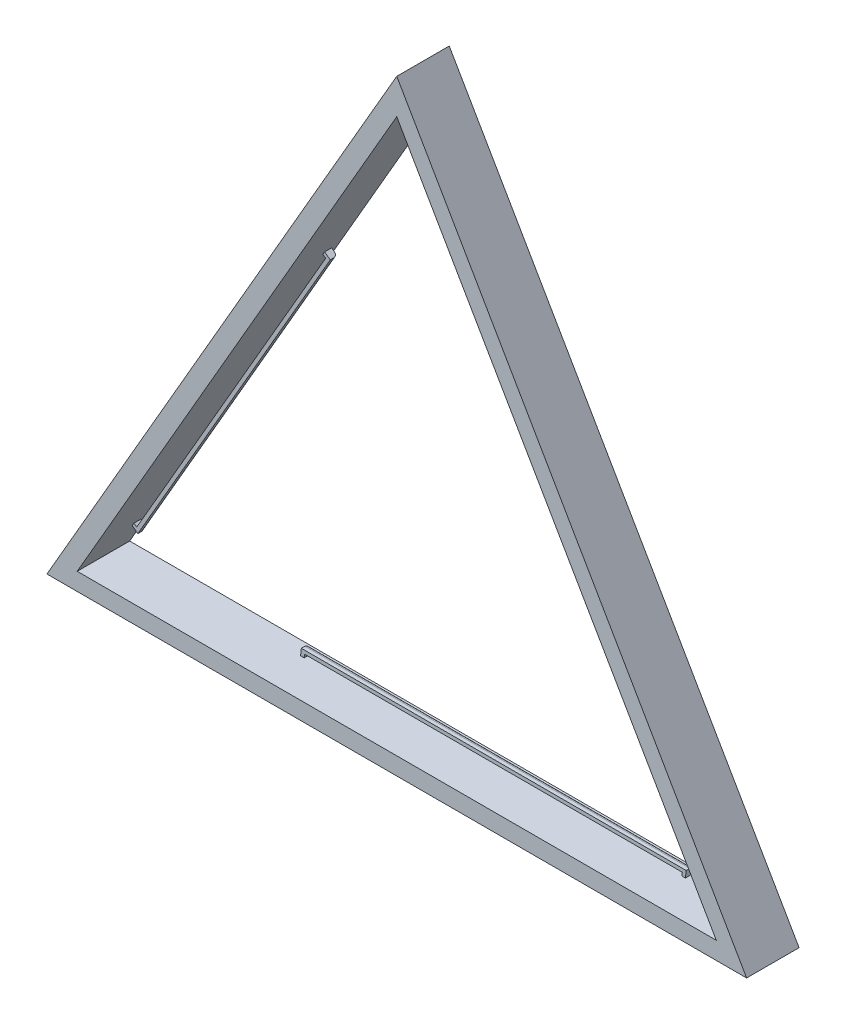
SolidWorks part; units mm, degrees
ref_plane "Plan de face" through (0, 0, 0) normal (0, 0, 1) x (1, 0, 0)
ref_plane "Plan de dessus" through (0, 0, 0) normal (0, 1, 0) x (1, 0, 0)
ref_plane "Plan de droite" through (0, 0, 0) normal (1, 0, 0) x (0, 0, -1)
sketch "Esquisse1" plane through (0, 0, 0) normal (0, 0, 1) x (1, 0, 0)
  line L0 (-46.8758, 92.3315) -> (-146.8758, -80.8736)
  line L1 (-146.8758, -80.8736) -> (53.1242, -80.8736)
  line L2 (53.1242, -80.8736) -> (-46.8758, 92.3315)
  line L3 (44.464, -75.8736) -> (-46.8758, 82.3315)
  line L4 (-46.8758, 82.3315) -> (-138.2155, -75.8736)
  line L5 (-138.2155, -75.8736) -> (44.464, -75.8736)
  dimension "D1" = 200
  dimension "D2" = 5
extrude "Boss.-Extru.1" add sketch "Esquisse1" along normal blind 15
sketch "Esquisse2" plane through (0, 0, 0) normal (0, 0, -1) x (-1, 0, 0)
  line L3 (-42.7319, -74.8736) -> (136.4835, -74.8736)
  line L4 (136.4835, -74.8736) -> (46.8758, 80.3315)
  line L5 (46.8758, 80.3315) -> (-42.7319, -74.8736)
  line L6 (-53.1242, -80.8736) -> (146.8758, -80.8736)
  line L7 (146.8758, -80.8736) -> (46.8758, 92.3315)
  line L8 (46.8758, 92.3315) -> (-53.1242, -80.8736)
  line L9 (-53.1242, -80.8736) -> (146.8758, -80.8736)
  line L10 (146.8758, -80.8736) -> (46.8758, 92.3315)
  line L11 (46.8758, 92.3315) -> (-53.1242, -80.8736)
  dimension "D1" = 5
  dimension "D2" = 6
extrude "Boss.-Extru.2" add sketch "Esquisse2" against normal blind 2
sketch "Esquisse3" plane through (0, 0, 2) normal (0, 0, 1) x (1, 0, 0)
  line L0 (-114.5698, -74.8736) -> (-127.3485, -74.8736) construction
  line L1 (-76.8846, 26.3892) -> (-131.8846, -68.8736)
  line L2 (-136.4835, -74.8736) -> (-46.8758, 80.3315) construction
  line L3 (-79.3071, 28.1588) -> (-134.3071, -67.104)
  line L4 (-134.3071, -67.104) -> (-131.8846, -68.8736)
  line L5 (-76.8846, 26.3892) -> (-79.3071, 28.1588)
  line L6 (-78.1997, 26.1114) -> (-78.9978, 26.6945)
  line L7 (-46.8758, 80.3315) -> (-46.8758, -74.8736) construction
  line L8 (42.7319, -74.8736) -> (-136.4835, -74.8736) construction
  line L13 (42.7319, -74.8736) -> (-91.6796, 2.7289) construction
  line L14 (-136.4835, -74.8736) -> (-2.0719, 2.7289) construction
  line L15 (-78.9978, 26.6945) -> (-132.992, -66.8262)
  line L16 (-132.992, -66.8262) -> (-132.1939, -67.4093)
  line L17 (-78.1997, 26.1114) -> (-132.1939, -67.4093)
  line L26 (-46.8758, 80.3315) -> (42.7319, -74.8736) construction
  line L52 (-138.2155, -75.8736) -> (-46.8758, 82.3315) construction
  line L61 (16.2171, -30.9141) -> (18.9609, -29.701)
  line L62 (18.9609, -29.701) -> (-36.0391, 65.5618)
  line L63 (-36.0391, 65.5618) -> (-38.7829, 64.3487)
  line L64 (16.2171, -30.9141) -> (-38.7829, 64.3487)
  line L65 (16.6341, -29.6363) -> (17.5381, -29.2366)
  line L66 (17.5381, -29.2366) -> (-36.4561, 64.2841)
  line L67 (-36.4561, 64.2841) -> (-37.3601, 63.8844)
  line L68 (16.6341, -29.6363) -> (-37.3601, 63.8844)
  line L69 (-84.2579, -74.8909) -> (-84.3638, -75.8736)
  line L70 (-84.3638, -75.8736) -> (23.6246, -75.8736)
  line L71 (23.6246, -75.8736) -> (23.7305, -74.8909)
  line L72 (-84.2579, -74.8909) -> (23.7305, -74.8909)
  line L73 (-85.156, -73.8909) -> (-85.4773, -76.8736)
  line L74 (-85.4773, -76.8736) -> (24.5227, -76.8736)
  line L75 (24.5227, -76.8736) -> (24.844, -73.8909)
  line L76 (-85.156, -73.8909) -> (24.844, -73.8909)
  dimension "D1" = 110
  dimension "D2" = 12
  dimension "D3" = 3
  dimension "D5" = 1
extrude "Boss.-Extru.5" add sketch "Esquisse3" along normal blind 2
fillet "Congé1" radius 1 3 edges at (-11.2829, 16.7173, 2) (-104.3846, -21.2422, 2) (-30.156, -73.8909, 2)
sketch3d "Esquisse3D1"
  line L0 (-138.2155, -75.8736, 0) -> (44.464, -75.8736, 0)
  line L1 (-46.8758, 82.3315, 0) -> (-138.2155, -75.8736, 0)
  line L2 (44.464, -75.8736, 0) -> (-46.8758, 82.3315, 0)
  line L3 (-138.2155, -75.8736, 0) -> (44.464, -75.8736, 0)
  line L4 (-46.8758, 82.3315, 0) -> (-138.2155, -75.8736, 0)
  line L5 (44.464, -75.8736, 0) -> (-46.8758, 82.3315, 0)
  line L6 (-136.4835, -74.8736, 0) -> (42.7319, -74.8736, 0)
  line L7 (-46.8758, 80.3315, 0) -> (-136.4835, -74.8736, 0)
  line L8 (42.7319, -74.8736, 0) -> (-46.8758, 80.3315, 0)
  line L9 (-136.4835, -74.8736, 0) -> (42.7319, -74.8736, 0)
  line L10 (-46.8758, 80.3315, 0) -> (-136.4835, -74.8736, 0)
  line L11 (42.7319, -74.8736, 0) -> (-46.8758, 80.3315, 0)
  dimension "D1" = 5
  dimension "D2" = 6
extrude "Enlèv. mat.-Extru.1" cut sketch "Esquisse3D1" along direction (0, 0, 1) on the side of the normal blind 2
